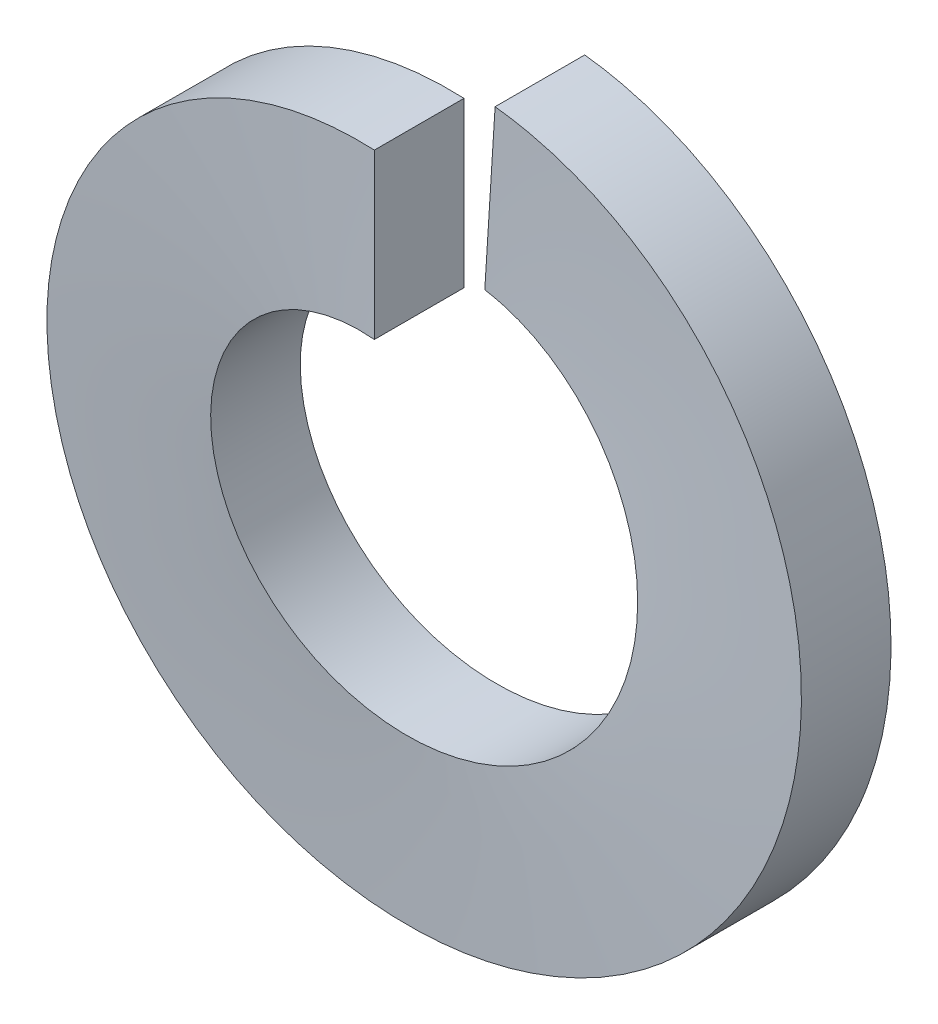
SolidWorks part; units mm, degrees
ref_plane "Front Plane" through (0, 0, 0) normal (0, 0, 1) x (1, 0, 0)
ref_plane "Top Plane" through (0, 0, 0) normal (0, 1, 0) x (1, 0, 0)
ref_plane "Right Plane" through (0, 0, 0) normal (1, 0, 0) x (0, 0, -1)
sketch "Sketch1" plane through (0, 0, 0) normal (0, 0, 1) x (1, 0, 0)
  line L0 (0, 6.1849) -> (0, 3.302) construction
  circle A0 centre (0, 0) radius 6.1849
  circle A1 centre (0, 0) radius 3.302 construction
  dimension "ID" = 6.604
  dimension "OD" = 12.3698
curve "Helix/Spiral1" pitch 1.7498 height 1.7323 radius 6.1849 left hand yes centre (0, 0, 0) axis (0, 0, -1) start towards (0, 1, 0) parameters "HT"=1.7323
sketch "Sketch2" plane through (0, 0, 0) normal (1, 0, 0) x (0, 0, -1)
  line L1 (0, 6.1849) -> (-1.5748, 6.1849)
  line L2 (0, 6.1849) -> (0, 3.302)
  line L3 (0, 3.302) -> (-1.5748, 3.302)
  line L4 (-1.5748, 6.1849) -> (-1.5748, 3.302)
  dimension "THK" = 1.5748
sweep "Sweep1" add profiles "Sketch2" path "Helix/Spiral1"
sketch "Sketch3" plane through (0, 0, 0) normal (0, 0, 1) x (1, 0, 0)
  circle A0 centre (0, 0) radius 3.302 construction
  spline S0 degree 2 poles (0, 3.302) (-1.0729, 3.302) (-1.941, 2.6713) (-2.809, 2.0407) (-3.1406, 1.0202) (-3.4721, -0.0002) (-3.1406, -1.0206) (-2.809, -2.0411) (-1.941, -2.6717) (-1.073, -3.3024) (0, -3.3024) (1.0729, -3.3024) (1.941, -2.6717) (2.809, -2.0411) (3.1406, -1.0206) (3.4721, -0.0002) (3.1406, 1.0202) (2.809, 2.0407) (1.941, 2.6713) (1.1648, 3.2352) (0.2074, 3.2955) (0.2074, 3.2955) (0.2074, 3.2955) knots 0 0 0 0.1 0.1 0.2 0.2 0.3 0.3 0.4 0.4 0.5 0.5 0.6 0.6 0.7 0.7 0.8 0.8 0.9 0.9 0.989879 0.989879 0.98988 0.98988 0.98988 weights 1 0.951057 1 0.951057 1 0.951057 1 0.951057 1 0.951057 1 0.951057 1 0.951057 1 0.951057 1 0.951057 1 0.95601 0.991096 0.991096 0.991096 construction
ref_plane "Plane1" through (0, 0, 1.5748) normal (0, 0, 1) x (1, 0, 0)
ref_plane "Plane2" through (0, 0, -1.7327) normal (0, 0, 1) x (1, 0, 0)
ref_axis "Axis1" through (0, 0, 0) along (0, 0, 1)
equation "\"HT@Helix/Spiral1\" = \"THK@Sketch2\"*1.1"
